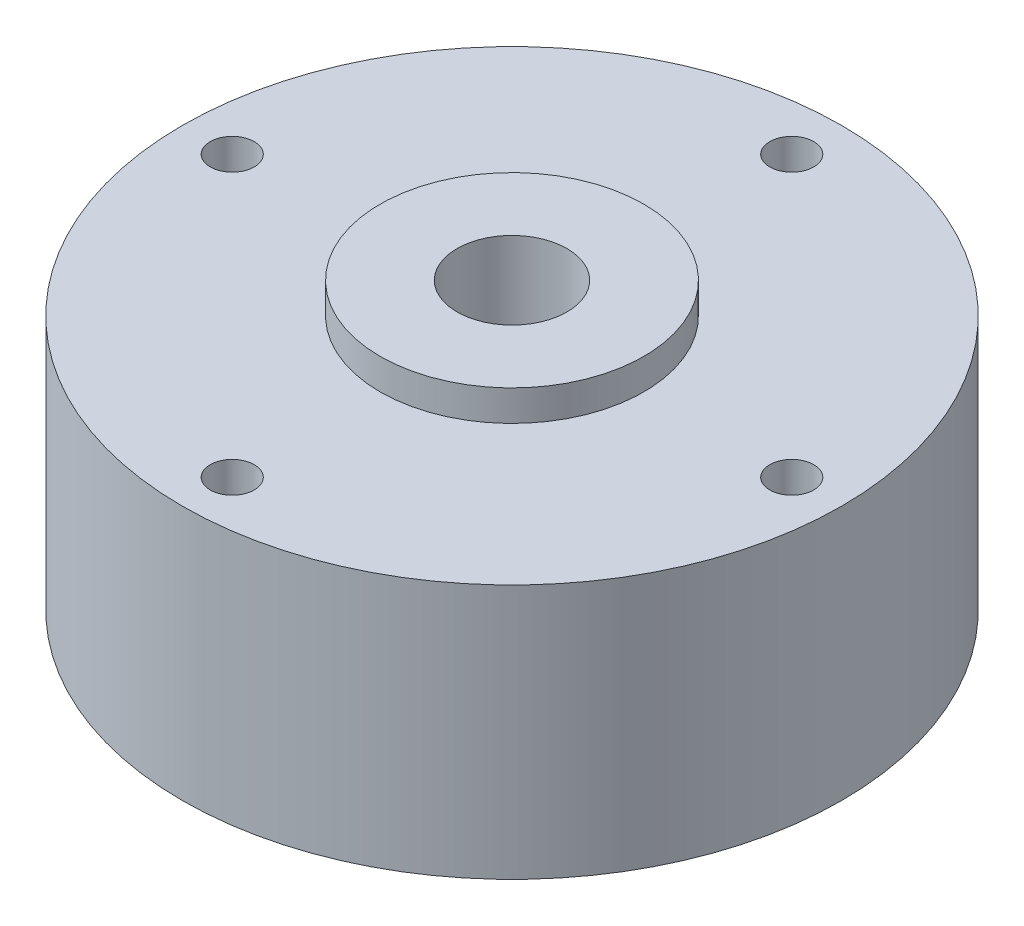
SolidWorks part; units mm, degrees
ref_plane "Front plane" through (0, 0, 0) normal (0, 0, 1) x (1, 0, 0)
ref_plane "Top plane" through (0, 0, 0) normal (0, 1, 0) x (1, 0, 0)
ref_plane "Right plane" through (0, 0, 0) normal (1, 0, 0) x (0, 0, -1)
ref_axis "Axis X" through (0, 0, 0) along (1, 0, 0)
ref_axis "Axis Y" through (0, 0, 0) along (0, 1, 0)
ref_axis "Axis Z" through (0, 0, 0) along (0, 0, 1)
sketch "Sketch1" plane through (0, 0, 0) normal (0, 1, 0) x (1, 0, 0)
  circle A0 centre (0, 0) radius 15
  dimension "D1" = 30
extrude "Extrude1" add sketch "Sketch1" along normal blind 13
sketch "Sketch2" plane through (0, 13, 0) normal (0, 1, 0) x (1, 0, 0)
  circle A0 centre (0, 0) radius 6
  circle A1 centre (0, 0) radius 15
  dimension "D1" = 30
  dimension "D2" = 12
extrude "Extrude2" cut sketch "Sketch2" against normal blind 1.4
sketch "Sketch3" plane through (0, 13, 0) normal (0, 1, 0) x (1, 0, 0)
  line L0 (0, 0) -> (0, 12.7279) construction
  circle A0 centre (0, 0) radius 12.7279 construction
  circle A1 centre (0, 12.7279) radius 1
  circle A2 centre (12.7279, 0) radius 1
  circle A3 centre (0, -12.7279) radius 1
  circle A4 centre (-12.7279, 0) radius 1
  dimension "D1" = 25.4558
  dimension "D2" = 2
extrude "Extrude3" cut sketch "Sketch3" against normal blind 4.4
sketch "Sketch4" plane through (0, 0, 0) normal (0, -1, 0) x (1, 0, 0)
  line L0 (0, 0) -> (0, 5) construction
  circle A0 centre (0, 0) radius 5 construction
  circle A1 centre (0, 5) radius 1
  circle A2 centre (5, 0) radius 1
  circle A3 centre (0, -5) radius 1
  circle A4 centre (-5, 0) radius 1
  dimension "D1" = 2
  dimension "D3" = 10
  dimension "D2" = 4
extrude "Extrude4" [suppressed] cut sketch "Sketch4" against normal blind 3
sketch "Sketch5" plane through (0, 0, 0) normal (0, -1, 0) x (1, 0, 0)
  line L1 (-11, 5) -> (11, 5) construction
  line L2 (-11, 5) -> (-11, -5) construction
  line L3 (-11, -5) -> (11, -5) construction
  line L4 (11, 5) -> (11, -5) construction
  line L5 (-11, 5) -> (11, -5) construction
  line L6 (-11, -5) -> (11, 5) construction
  circle A0 centre (-11, 5) radius 1
  circle A1 centre (11, 5) radius 1
  circle A2 centre (11, -5) radius 1
  circle A3 centre (-11, -5) radius 1
  point P0 (0, 0)
  dimension "D2" = 2
  dimension "D1" = 2
  dimension "D3" = 2
  dimension "D4" = 2
  dimension "D5" = 22
  dimension "D6" = 10
extrude "Extrude5" cut sketch "Sketch5" against normal blind 3
chamfer "Chamfer1" [suppressed] distance 0.5 angle 45
sketch "Sketch6" plane through (0, 0, 0) normal (0, -1, 0) x (1, 0, 0)
  circle A0 centre (0, 0) radius 2.5
  dimension "D1" = 5
extrude "Extrude6" cut sketch "Sketch6" against normal through all
equation "\"motor_D\"= 30'Motor diameter"
equation "\"motor_H\"= 13'Motor heigh"
equation "\"motor_d1\"= 25.4558'Seating diameter of screws on the fixed part of the motor"
equation "\"motor_s1\"= 2'Screws diameter on the fixed part of motor"
equation "\"motor_d2\"= 0'Seating diameter of screws on the moving part of the motor (if this parameter is not determine, write 0)"
equation "\"motor_s2\"= 2'Screws diameter on the moving part of motor"
equation "\"motor_Dc\"= 5'Central hole diameter of motor"
equation "\"bearing_d1\"= 6'Bearing inner diameter"
equation "\"bearing_d2\"= 17'Bearing external diameter"
equation "\"bearing h\"= 6'Bearing heigh"
equation "\"pin_d\"= 2'Pin diameter"
equation "\"pin_h\"= 12'Pin heigh"
equation "\"magnet_d1\"= 5'Magnet inner diameter"
equation "\"magnet_d2\"= 9.5'Magnet external diameter"
equation "\"magnet_h\"= 3'Magnet heigh"
equation "\"motor_a2\"= 10'Seating parameter in rectangle of screws on the moving part of the motor"
equation "\"motor_b2\"= 22'Seating parameter in rectangle of screws on the moving part of the motor"
equation "\"D1@Sketch1\"=\"motor_D\""
equation "\"D1@Extrude1\"=\"motor_H\""
equation "\"D1@Sketch2\"=\"motor_D\""
equation "\"motor_cmd\"= 12'Central magnet mount diameter"
equation "\"motor_cmh\"= 1.4'Central magnet mount heigh (if not write 0)"
equation "\"D2@Sketch2\"=\"motor_cmd\""
equation "\"D1@Extrude2\"= \"motor_cmh\""
equation "\"Extrude2\"= IIF ( \"motor_cmh\" = 0 , \"suppressed\" , \"unsuppressed\" )"
equation "\"D1@Sketch3\"=\"motor_d1\""
equation "\"D2@Sketch3\"=\"motor_s1\""
equation "\"D1@Extrude3\"=\"motor_cmh\"+3"
equation "\"D1@Sketch4\"=\"motor_s2\""
equation "\"D3@Sketch4\"=if( \"motor_d2\"=0,10,\"motor_d2\")"
equation "\"Extrude4\"= IIF ( \"motor_d2\" = 0 , \"suppressed\" , \"unsuppressed\" )"
equation "\"D1@Sketch5\"=\"motor_s2\""
equation "\"D2@Sketch5\"=\"D1@Sketch5\""
equation "\"D3@Sketch5\"=\"D2@Sketch5\""
equation "\"D4@Sketch5\"=\"D2@Sketch5\""
equation "\"D5@Sketch5\"=\"motor_b2\""
equation "\"D6@Sketch5\"=\"motor_a2\""
equation "\"Extrude5\"= IIF ( \"motor_d2\" = 0 , \"unsuppressed\" , \"suppressed\" )"
equation "\"D1@Sketch6\"=\"motor_Dc\""
equation "\"motor_whR\"= 10'Distance from center of motor to wires"
equation "\"print_offset\"= 0.2'Offset for printing holes"
equation "\"ft_sensor_d1\"= 9.8"
equation "\"ft_sensor_d2\"= 24.9"
equation "\"ft_sensor_d3\"= 22.6'Inner diameter of "
equation "\"ft_sensor_h\"= 7.1"
equation "\"ft_sensor_whD\"= 5"
